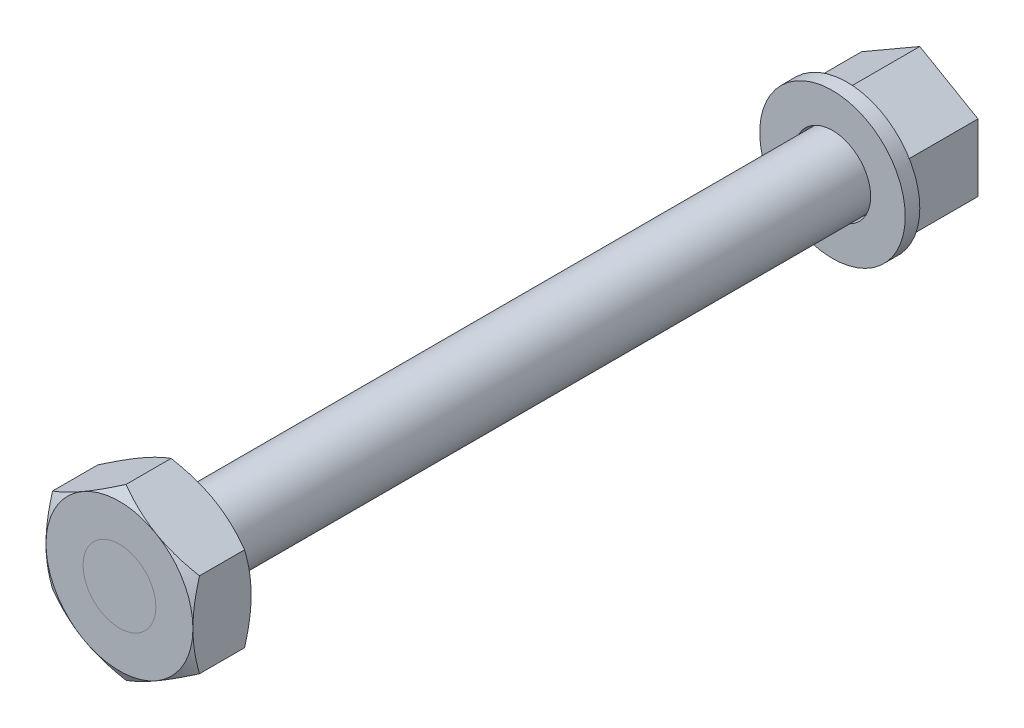
SolidWorks part; units mm, degrees
other "Dado"
other "Rosetta"
other "Vite"
ref_plane "Piano frontale" through (0, 0, 0) normal (0, 0, 1) x (1, 0, 0)
ref_plane "Piano superiore" through (0, 0, 0) normal (0, 1, 0) x (1, 0, 0)
ref_plane "Piano destro" through (0, 0, 0) normal (1, 0, 0) x (0, 0, -1)
sketch "Sketch1" plane through (0, 0, 0) normal (0, 0, 1) x (1, 0, 0)
  line L1 (-3.1632, 12.1549) -> (-11.1632, 16.7737)
  line L2 (-11.1632, 16.7737) -> (-19.1632, 12.1549)
  line L3 (-19.1632, 12.1549) -> (-19.1632, 2.9173)
  line L4 (-19.1632, 2.9173) -> (-11.1632, -1.7015)
  line L5 (-11.1632, -1.7015) -> (-3.1632, 2.9173)
  line L6 (-3.1632, 2.9173) -> (-3.1632, 12.1549)
  circle A0 centre (-11.1632, 7.5361) radius 8 construction
  circle A1 centre (-11.1632, 7.5361) radius 5
  dimension "D1" = 10
  dimension "D2" = 16
extrude "Boss-Extrude1" add sketch "Sketch1" along normal blind 10 contours A1 | L5 L6 L1 L2 L3 L4 A1 region at (-3.4076, 7.5361, 0) region at (-11.1632, 7.5361, 0)
extrude "Boss-Extrude2" add sketch "Sketch1<3>" along normal blind 100 from surface contours A1 region at (-11.1632, 7.5361, 0) starting at face at (-11.1632, 7.5361, 10)
sketch "Sketch1<3>" plane through (0, 0, 0) normal (0, 0, 1) x (1, 0, 0) same geometry as "Sketch1"
sketch "Sketch3" plane through (0, 0, 0) normal (0, 0, 1) x (1, 0, 0)
  circle A0 centre (-11.1632, 7.5361) radius 10
  circle A1 centre (-11.1632, 7.5361) radius 5 construction
  circle A2 centre (-11.1632, 7.5361) radius 5.25
  dimension "D1" = 20
  dimension "D2" = 10.5
extrude "Boss-Extrude3" add sketch "Sketch3" along normal blind 2 from surface separate body starting at face at (-6.1632, 7.5361, 10)
sketch "Sketch4" plane through (0, 0, 110) normal (0, 0, 1) x (1, 0, 0)
  line L7 (-19.1632, 12.1549) -> (-19.1632, 2.9173) construction
  line L8 (-11.1632, -4.1236) -> (-1.0656, 1.7062)
  line L9 (-1.0656, 1.7062) -> (-1.0656, 13.366)
  line L10 (-1.0656, 13.366) -> (-11.1632, 19.1958)
  line L11 (-11.1632, 19.1958) -> (-21.2608, 13.366)
  line L12 (-21.2608, 13.366) -> (-21.2608, 1.7062)
  line L13 (-21.2608, 1.7062) -> (-11.1632, -4.1236)
  circle A3 centre (-11.1632, 7.5361) radius 10.0976 construction
  circle A4 centre (-11.1632, 7.5361) radius 5 construction
  circle A5 centre (-11.1632, 7.5361) radius 5
extrude "Boss-Extrude4" add sketch "Sketch4" against normal blind 8 separate body
ref_plane "Plane1" through (0, 7.5361, 0) normal (0, -1, 0) x (-1, 0, 0)
sketch "Sketch5" plane through (0, 7.5361, 0) normal (0, -1, 0) x (-1, 0, 0)
  line L0 (28.189, -106) -> (14.3326, -114)
  line L1 (14.3326, -114) -> (14.3326, -118.5)
  line L2 (14.3326, -118.5) -> (39.3326, -118.5)
  line L3 (39.3326, -118.5) -> (39.3326, -93.5)
  line L4 (39.3326, -93.5) -> (14.3326, -93.5)
  line L5 (14.3326, -93.5) -> (14.3326, -98)
  line L6 (14.3326, -98) -> (28.189, -106)
  line L7 (14.3326, -114) -> (20.4964, -114) construction
  line L8 (14.3326, -98) -> (20.7305, -98) construction
  point P7 (21.2608, -110)
  point P10 (21.2608, -102)
  dimension "D1" = 30
  dimension "D2" = 30
  dimension "D3" = 25
  dimension "D4" = 25
ref_plane "Plane2" through (-11.1632, 0, 0) normal (1, 0, 0) x (0, 0, -1)
ref_axis "Axis1" through (-11.1632, 7.5361, 111.6) along (0, 0, 1)
revolve "Cut-Revolve1" cut sketch "Sketch5" angle 360 about axis through (-11.1632, 7.5361, 111.6) along (0, 0, 1)
